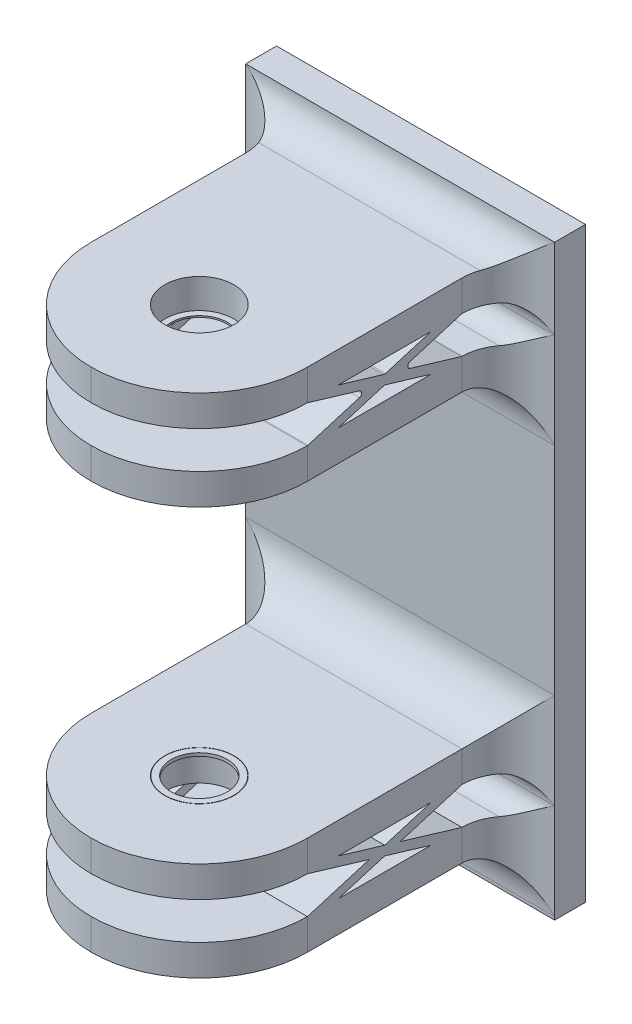
SolidWorks part; units mm, degrees
ref_plane "Plan de face" through (0, 0, 0) normal (1, 0, 0) x (0, 1, 0)
ref_plane "Plan de dessus" through (0, 0, 0) normal (0, 0, 1) x (0, 1, 0)
ref_plane "Plan de droite" through (0, 0, 0) normal (0, 1, 0) x (-1, 0, 0)
sketch "Esquisse1" plane through (0, 0, 0) normal (0, 0, 1) x (0, 1, 0)
  line L1 (0, 0) -> (180, 0)
  line L2 (0, 0) -> (0, 100)
  line L3 (0, 100) -> (180, 100)
  line L4 (180, 0) -> (180, 100)
  dimension "D1" = 180
  dimension "D2" = 100
extrude "Boss.-Extru.1" add sketch "Esquisse1" along normal blind 10
sketch "Esquisse2" plane through (0, 0, 10) normal (0, 0, 1) x (1, 0, 0)
  line L0 (-100, 180) -> (-100, 0) construction
  line L1 (-85, 158) -> (-15, 158)
  line L2 (-85, 158) -> (-85, 148)
  line L3 (-85, 148) -> (-15, 148)
  line L4 (-15, 158) -> (-15, 148)
  line L5 (-85, 180) -> (-15, 180)
  line L6 (0, 0) -> (0, 180) construction
  line L7 (0, 180) -> (-100, 180) construction
  line L8 (-85, 48) -> (-15, 48)
  line L9 (-85, 48) -> (-85, 38)
  line L10 (-85, 38) -> (-15, 38)
  line L11 (-15, 48) -> (-15, 38)
  line L12 (-85, 180) -> (-85, 170)
  line L13 (-85, 170) -> (-15, 170)
  line L14 (-15, 180) -> (-15, 170)
  line L16 (-85, 26) -> (-15, 26)
  line L17 (-85, 26) -> (-85, 16)
  line L18 (-85, 16) -> (-15, 16)
  line L19 (-15, 26) -> (-15, 16)
  dimension "D1" = 10
  dimension "D2" = 10
  dimension "D3" = 100
  dimension "D4" = 70
  dimension "D5" = 15
  dimension "D6" = 70
  dimension "D7" = 15
  dimension "D8" = 12
  dimension "D9" = 70
  dimension "D10" = 10
  dimension "D11" = 15
  dimension "D12" = 70
  dimension "D13" = 10
  dimension "D14" = 12
extrude "Boss.-Extru.2" add sketch "Esquisse2" along normal blind 100
fillet "Congé1" radius 35 8 edges at (-85, 153, 110) (-15, 153, 110) (-15, 43, 110) (-85, 43, 110) (-85, 175, 110) (-15, 175, 110) (-15, 21, 110) (-85, 21, 110)
sketch "Esquisse3" plane through (0, 180, 0) normal (0, 1, 0) x (-1, 0, 0)
  line L0 (0, 10) -> (0, 0) construction
  line L2 (0, 0) -> (100, 0) construction
  circle A0 centre (50, 75) radius 11.2
  dimension "D3" = 22.4
  dimension "D1" = 50
  dimension "D2" = 75
extrude "Enlèv. mat.-Extru.1" cut sketch "Esquisse3" against normal blind 208
fillet "Congé2" radius 15 11 edges at (-15, 43, 10) (-50, 48, 10) (-85, 43, 10) (-85, 175, 10) (-15, 175, 10) (-15, 153, 10) (-50, 148, 10) (-85, 153, 10) (-85, 21, 10) (-15, 21, 10) (-50, 16, 10)
fillet "Congé3" radius 6 2 edges at (-50, 170, 10) (-50, 158, 10)
sketch "Esquisse5" plane through (-85, 0, 0) normal (-1, 0, 0) x (0, -1, 0)
  line L0 (-170, 75) -> (-158, 35)
  line L1 (-158, 75) -> (-158, 25) construction
  line L2 (-158, 35) -> (-158, 25)
  line L3 (-158, 25) -> (-170, 65)
  line L4 (-170, 75) -> (-170, 25) construction
  line L5 (-170, 65) -> (-170, 75)
  dimension "D1" = 10
  dimension "D2" = 10
extrude "Boss.-Extru.3" add sketch "Esquisse5" against normal blind 17
sketch "Esquisse7" plane through (-85, 0, 0) normal (-1, 0, 0) x (0, -1, 0)
  line L0 (-170, 25) -> (-170, 35)
  line L1 (-170, 25) -> (-158, 65)
  line L2 (-170, 35) -> (-158, 75)
  line L3 (-158, 65) -> (-158, 75)
  line L4 (-170, 65) -> (-170, 25) construction
  dimension "D1" = 10
extrude "Boss.-Extru.6" add sketch "Esquisse7" against normal blind 17
fillet "Congé4" radius 10 1 edges at (-76.5, 170, 75)
ref_axis "Axe1" through (-50, 180, 0) along (0, 0, 1)
ref_axis "Axe2" through (-50, 16, 110) along (0, 0, -1)
ref_plane "Plan1" through (-50, 0, 0) normal (1, 0, 0) x (0, 0, -1)
mirror "Symétrie1" about plane through (-50, 0, 0) normal (1, 0, 0) of "Boss.-Extru.3", "Boss.-Extru.6"
sketch "Esquisse10" plane through (0, 48, 0) normal (0, 1, 0) x (-1, 0, 0)
  circle A0 centre (50, 75) radius 11.0955
  circle A1 centre (50, 75) radius 9.0955
  dimension "D1" = 2
extrude "Boss.-Extru.7" add sketch "Esquisse10" against normal blind 1 separate body
sketch "Esquisse11" plane through (0, 148, 0) normal (0, -1, 0) x (1, 0, 0)
  circle A0 centre (-50, 75) radius 11.2
  circle A1 centre (-50, 75) radius 9.0955
extrude "Boss.-Extru.8" add sketch "Esquisse11" against normal blind 1
sketch "Esquisse13" plane through (0, 0, 0) normal (1, 0, 0) x (0, 1, 0)
  line L0 (164, 10) -> (180, 10) construction
  line L1 (180, 0) -> (190, 0)
  line L2 (180, 0) -> (180, 10)
  line L3 (180, 10) -> (190, 10)
  line L4 (190, 0) -> (190, 10)
  dimension "D1" = 0
  dimension "D2" = 10
extrude "Boss.-Extru.9" add sketch "Esquisse13" against normal blind 100
fillet "Congé6" radius 10 1 edges at (-50, 180, 10)
fillet "Congé7" radius 6 2 edges at (-50, 26, 10) (-50, 38, 10)
sketch "Esquisse14" plane through (0, 170, 0) normal (0, -1, 0) x (1, 0, 0)
  circle A0 centre (-50, 75) radius 11.0955
  circle A1 centre (-50, 75) radius 9.0955
extrude "Boss.-Extru.10" add sketch "Esquisse14" against normal blind 0.5 separate body
sketch "Esquisse15" plane through (0, 26, 0) normal (0, 1, 0) x (-1, 0, 0)
  circle A0 centre (50, 75) radius 11.0955
  circle A1 centre (50, 75) radius 9.0955
extrude "Boss.-Extru.11" add sketch "Esquisse15" against normal blind 0.5 separate body
sketch "Esquisse16" plane through (-15, 0, 0) normal (1, 0, 0) x (0, 1, 0)
  line L0 (26, 25) -> (26, 35)
  line L1 (26, 25) -> (38, 65)
  line L2 (26, 35) -> (38, 75)
  line L3 (38, 65) -> (38, 75)
  line L4 (26, 75) -> (26, 25) construction
  dimension "D1" = 10
extrude "Boss.-Extru.12" add sketch "Esquisse16" against normal blind 17
sketch "Esquisse17" plane through (-15, 0, 0) normal (1, 0, 0) x (0, 1, 0)
  line L0 (26, 75) -> (26, 65)
  line L1 (26, 75) -> (38, 35)
  line L2 (26, 65) -> (38, 25)
  line L3 (38, 35) -> (38, 25)
  line L4 (26, 75) -> (26, 35) construction
  dimension "D1" = 10
extrude "Boss.-Extru.13" add sketch "Esquisse17" against normal blind 17
mirror "Symétrie2" about plane through (-50, 0, 0) normal (1, 0, 0) of "Boss.-Extru.12", "Boss.-Extru.13"
fillet "Congé8" radius 1 15 edges at (-23.5, 158, 25) (-23.5, 170, 25) (-23.5, 158, 75) (-23.5, 170, 75) (-23.5, 162.5, 50) (-23.5, 164, 45) (-23.5, 165.5, 50) (-76.5, 170, 25) (-76.5, 158, 25) (-76.5, 158, 75) (-76.5, 164, 45) (-76.5, 165.5, 50) (-76.5, 162.5, 50) (-23.5, 164, 55) (-76.5, 164, 55)
